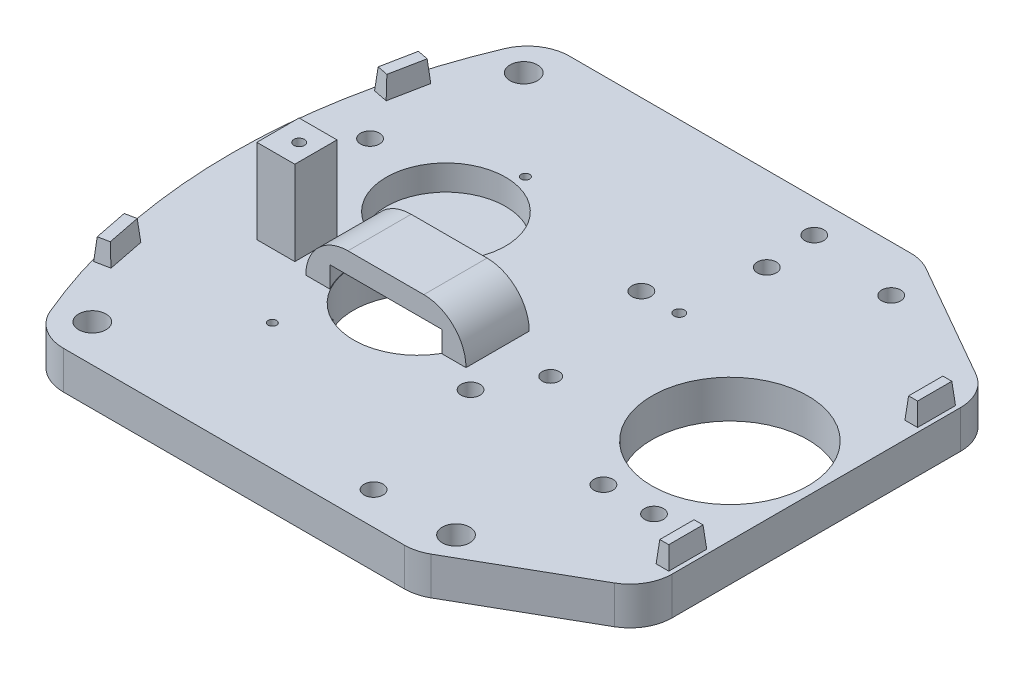
SolidWorks part; units mm, degrees
ref_plane "Front" through (0, 0, 0) normal (0, 0, 1) x (1, 0, 0)
ref_plane "Top" through (0, 0, 0) normal (0, 1, 0) x (1, 0, 0)
ref_plane "Right" through (0, 0, 0) normal (1, 0, 0) x (0, 0, -1)
sketch "Sketch1" plane through (0, 0, 0) normal (0, 1, 0) x (1, 0, 0)
  line L0 (125, 60) -> (3.8854, 60) construction
  line L1 (0, 0) -> (125, 0)
  line L2 (0, 0) -> (0, 120)
  line L3 (0, 120) -> (125, 120)
  line L4 (125, 0) -> (125, 120)
  line L5 (3.8854, 127.5) -> (3.8854, -7.5) construction
  arc A0 (3.8854, 127.5) -> (3.8854, -7.5) centre (125, 60) ccw
  dimension "D1" = 125
  dimension "D2" = 120
  dimension "D3" = 135
extrude "Top_Base" add sketch "Sketch1" along normal blind 9 contours L2 A0 | L1 L4 L3 L2 region at (62.5, 0, -60) region at (-5.4854, 0, -60)
sketch "Fingers_Position" plane through (0, 9, 0) normal (0, 1, 0) x (1, 0, 0)
  line L5 (67.75, 3.25) -> (12.75, 3.25) construction
  line L6 (67.75, 3.25) -> (67.75, 35.25) construction
  line L7 (67.75, 35.25) -> (12.75, 35.25) construction
  line L8 (12.75, 3.25) -> (12.75, 35.25) construction
  line L10 (67.75, 19.25) -> (26, 19.25) construction
  line L11 (77.75, 104.5) -> (77.75, 49.5) construction
  line L12 (35.75, 35.25) -> (35.75, 3.25) construction
  line L13 (40.75, 35.25) -> (40.75, 3.25) construction
  line L14 (125, 60) -> (-13.6542, 60) construction
  line L15 (35.75, 84.75) -> (35.75, 116.75) construction
  line L16 (26, 19.25) -> (26, 30) construction
  line L18 (77.75, 49.5) -> (109.75, 49.5) construction
  line L19 (109.75, 49.5) -> (109.75, 104.5) construction
  line L20 (109.75, 104.5) -> (77.75, 104.5) construction
  line L21 (92.5, 69) -> (92.5, 31) construction
  line L22 (92.5, 31) -> (116.5, 31) construction
  line L23 (116.5, 31) -> (116.5, 69) construction
  line L24 (116.5, 69) -> (92.5, 69) construction
  line L25 (93.75, 104.5) -> (93.75, 60) construction
  line L26 (104.5, 31) -> (104.5, 60) construction
  line L27 (26, 100.75) -> (26, 90) construction
  line L28 (40.75, 84.75) -> (40.75, 116.75) construction
  line L29 (67.75, 100.75) -> (26, 100.75) construction
  line L30 (12.75, 116.75) -> (12.75, 84.75) construction
  line L31 (67.75, 84.75) -> (12.75, 84.75) construction
  line L32 (67.75, 116.75) -> (67.75, 84.75) construction
  line L33 (67.75, 116.75) -> (12.75, 116.75) construction
  line L34 (26, 72.5) -> (26, 47.5) construction
  line L35 (92.5, 36) -> (98.5, 36) construction
  line L36 (98.5, 36) -> (98.5, 31) construction
  line L37 (116.5, 36) -> (110.5, 36) construction
  line L38 (110.5, 36) -> (110.5, 31) construction
  line L39 (93.75, 60) -> (104.5, 60) construction
  line L40 (77.75, 77.5) -> (109.75, 77.5) construction
  line L41 (125, 0) -> (125, 120) construction
  line L42 (67.75, 75.75) -> (58.75, 75.75) construction
  line L43 (67.75, 35.25) -> (58.75, 35.25) construction
  line L44 (67.75, 35.25) -> (67.75, 44.25) construction
  line L45 (67.75, 44.25) -> (58.75, 44.25) construction
  line L46 (58.75, 35.25) -> (58.75, 44.25) construction
  line L47 (58.75, 84.75) -> (58.75, 75.75) construction
  line L48 (67.75, 84.75) -> (58.75, 84.75) construction
  line L49 (67.75, 84.75) -> (67.75, 75.75) construction
  circle A1 centre (26, 30) radius 16.25 construction
  circle A3 centre (26, 30) radius 17.5 construction
  circle A5 centre (26, 30) radius 15 construction
  circle A6 centre (104.5, 60) radius 9 construction
  circle A7 centre (104.5, 60) radius 17.75 construction
  circle A8 centre (26, 30) radius 1 construction
  circle A9 centre (39.1696, 51.25) radius 7.5 construction
  circle A10 centre (39.1696, 51.25) radius 8.75 construction
  circle A11 centre (39.1696, 51.25) radius 10 construction
  circle A12 centre (39.1696, 68.75) radius 10 construction
  circle A13 centre (39.1696, 68.75) radius 8.75 construction
  circle A14 centre (39.1696, 68.75) radius 7.5 construction
  circle A15 centre (26, 90) radius 1 construction
  circle A16 centre (26, 90) radius 15 construction
  circle A17 centre (26, 90) radius 17.5 construction
  circle A18 centre (26, 90) radius 16.25 construction
  circle A19 centre (98.5, 36) radius 2.25 construction
  circle A20 centre (110.5, 36) radius 2.25 construction
  arc A21 (0, 120) -> (0, 0) centre (125, 60) ccw construction
  dimension "D3" = 32.5
  dimension "D4" = 35
  dimension "D6" = 30
  dimension "D10" = 18
  dimension "D11" = 35.5
  dimension "D19" = 2
  dimension "D20" = 20
  dimension "D21" = 17.5
  dimension "D22" = 15
  dimension "D29" = 4.5
  dimension "D5" = 32
  dimension "D7" = 55
  dimension "D8" = 24
  dimension "D9" = 38
  dimension "D14" = 10
  dimension "D2" = 27
  dimension "D15" = 55
  dimension "D16" = 32
  dimension "D17" = 41.75
  dimension "D18" = 10.75
  dimension "D23" = 25
  dimension "D13" = 29
  dimension "D25" = 6
  dimension "D26" = 6
  dimension "D27" = 5
  dimension "D28" = 5
  dimension "D12" = 44.5
  dimension "D30" = 10.75
  dimension "D31" = 27
  dimension "D24" = 8.5
  dimension "D32" = 32
  dimension "D33" = 9
  dimension "D34" = 9
sketch "Intermediate_Gear_Position" plane through (0, 9, 0) normal (0, 1, 0) x (1, 0, 0)
  line L0 (-5.25, 73.4139) -> (23.75, 73.4139) construction
  line L1 (35.75, 84.75) -> (35.75, 116.75) construction
  line L2 (32.75, 85.4139) -> (32.75, 61.4139) construction
  line L3 (-0.25, 79.4139) -> (-0.25, 85.4139) construction
  line L4 (32.75, 85.4139) -> (-5.25, 85.4139) construction
  line L6 (-5.25, 85.4139) -> (-5.25, 61.4139) construction
  line L7 (32.75, 61.4139) -> (-5.25, 61.4139) construction
  line L21 (-0.25, 67.4139) -> (-0.25, 61.4139) construction
  circle A0 centre (39.1696, 51.25) radius 14 construction
  circle A4 centre (39.1696, 51.25) radius 15 construction
  circle A6 centre (23.75, 73.4139) radius 14 construction
  circle A8 centre (39.1696, 51.25) radius 13 construction
  circle A10 centre (-0.25, 67.4139) radius 2.25 construction
  circle A11 centre (23.75, 73.4139) radius 13 construction
  circle A12 centre (-0.25, 79.4139) radius 2.25 construction
  circle A13 centre (23.75, 73.4139) radius 12 construction
  dimension "D2" = 30
  dimension "D6" = 28
  dimension "D4" = 26
  dimension "D18" = 4.5
  dimension "D22" = 4.5
  dimension "D3" = 28
  dimension "D10" = 26
  dimension "D11" = 24
  dimension "D8" = 38
  dimension "D5" = 6
  dimension "D7" = 24
  dimension "D16" = 5
  dimension "D19" = 6
  dimension "D21" = 5
  dimension "D9" = 29
  dimension "D12" = 3
sketch "Sketch5" plane through (0, 9, 0) normal (0, 1, 0) x (1, 0, 0)
  circle A1 centre (23.75, 73.4139) radius 14.15
  dimension "D1" = 28.3
extrude "Drive_Gear_Hole" cut sketch "Sketch5" against normal blind 6
sketch "Sketch8" plane through (0, 9, 0) normal (0, 1, 0) x (1, 0, 0)
  circle A1 centre (104.5, 60) radius 18.5
  dimension "D2" = 37
sketch "Sketch28" plane through (0, 9, 0) normal (0, 1, 0) x (1, 0, 0)
  circle A0 centre (39.1696, 51.25) radius 15.15
  dimension "D1" = 30.3
extrude "Two_Stage_Gear_Hole" cut sketch "Sketch28" against normal through all
extrude "XL320_Finger_Knuckle_Mount" cut sketch "Sketch8" against normal through all
sketch "XL320_Mount_Holes" plane through (0, 9, 0) normal (0, 1, 0) x (1, 0, 0)
  line L0 (116.5, 36) -> (110.5, 36) construction
  circle A13 centre (110.5, 36) radius 2.25
  circle A15 centre (98.5, 36) radius 2.25
  circle A16 centre (-0.25, 79.4139) radius 2.25
  circle A17 centre (-0.25, 67.4139) radius 2.25
  dimension "D5" = 4.5
sketch "AX12_Mount_Holes" plane through (0, 9, 0) normal (0, 1, 0) x (1, 0, 0)
  line L0 (67.75, 116.75) -> (72.25, 116.75) construction
  line L1 (67.75, 116.75) -> (12.75, 116.75) construction
  line L2 (72.25, 116.75) -> (72.25, 112.25) construction
  line L3 (67.75, 84.75) -> (67.75, 80.25) construction
  line L4 (67.75, 80.25) -> (63.25, 80.25) construction
  line L5 (93.75, 104.5) -> (93.75, 109) construction
  line L7 (109.75, 104.5) -> (77.75, 104.5) construction
  line L8 (77.75, 104.5) -> (73.25, 104.5) construction
  line L9 (73.25, 104.5) -> (73.25, 100) construction
  line L10 (67.75, 35.25) -> (67.75, 39.75) construction
  line L11 (67.75, 39.75) -> (63.25, 39.75) construction
  line L12 (67.75, 3.25) -> (72.25, 3.25) construction
  line L13 (67.75, 3.25) -> (12.75, 3.25) construction
  line L14 (72.25, 3.25) -> (72.25, 7.75) construction
  circle A4 centre (72.25, 112.25) radius 2.25
  circle A5 centre (63.25, 80.25) radius 2.25
  circle A6 centre (73.25, 100) radius 2.25
  circle A7 centre (93.75, 109) radius 2.25
  circle A8 centre (63.25, 39.75) radius 2.25
  circle A9 centre (72.25, 7.75) radius 2.25
  dimension "D2" = 4.5
  dimension "D1" = 4.5
sketch "Sketch26" plane through (0, 9, 0) normal (0, -1, 0) x (1, 0, 0)
  line L0 (26, -12.5) -> (26, -30) construction
  line L2 (-13.6542, -60) -> (125, -60) construction
  circle A0 centre (26, -30) radius 17.5 construction
  circle A1 centre (26, -30) radius 1
  circle A2 centre (26, -90) radius 1
  dimension "D2" = 2
extrude "String_Holes" cut sketch "Sketch26" along normal through all
extrude "XL320_Mount_Holes_(M4)" cut sketch "XL320_Mount_Holes" against normal through all
extrude "AX12_Mount_Holes_(M4)" cut sketch "AX12_Mount_Holes" against normal through all
sketch "Sketch27" plane through (0, 0, 0) normal (0, -1, 0) x (1, 0, 0)
  line L0 (110.5, -31.9585) -> (107, -33.9793)
  line L2 (107, -33.9793) -> (107, -38.0207)
  line L3 (107, -38.0207) -> (110.5, -40.0415)
  line L5 (110.5, -40.0415) -> (114, -38.0207)
  line L6 (114, -38.0207) -> (114, -33.9793)
  line L8 (114, -33.9793) -> (110.5, -31.9585)
  line L13 (110.5, -31.9585) -> (110.5, -40.0415) construction
  line L14 (107, -33.9793) -> (114, -38.0207) construction
  line L16 (114, -33.9793) -> (107, -38.0207) construction
  line L17 (98.5, -31.9585) -> (95, -33.9793)
  line L18 (95, -33.9793) -> (102, -38.0207) construction
  line L19 (95, -33.9793) -> (95, -38.0207)
  line L20 (102, -33.9793) -> (95, -38.0207) construction
  line L21 (98.5, -31.9585) -> (98.5, -40.0415) construction
  line L22 (102, -38.0207) -> (102, -33.9793)
  line L23 (95, -38.0207) -> (98.5, -40.0415)
  line L24 (98.5, -40.0415) -> (102, -38.0207)
  line L25 (102, -33.9793) -> (98.5, -31.9585)
  line L26 (3.25, -65.3931) -> (-0.25, -63.3724)
  line L27 (3.25, -69.4346) -> (3.25, -65.3931)
  line L28 (-3.75, -65.3931) -> (-3.75, -69.4346)
  line L29 (-0.25, -63.3724) -> (-0.25, -71.4553) construction
  line L30 (-3.75, -65.3931) -> (3.25, -69.4346) construction
  line L31 (-0.25, -63.3724) -> (-3.75, -65.3931)
  line L32 (-0.25, -71.4553) -> (3.25, -69.4346)
  line L33 (-3.75, -69.4346) -> (-0.25, -71.4553)
  line L34 (3.25, -65.3931) -> (-3.75, -69.4346) construction
  line L35 (-3.75, -77.3931) -> (3.25, -81.4346) construction
  line L36 (-3.75, -77.3931) -> (-3.75, -81.4346)
  line L37 (-0.25, -83.4553) -> (3.25, -81.4346)
  line L38 (-0.25, -75.3724) -> (-3.75, -77.3931)
  line L39 (3.25, -81.4346) -> (3.25, -77.3931)
  line L40 (-0.25, -75.3724) -> (-0.25, -83.4553) construction
  line L41 (3.25, -77.3931) -> (-0.25, -75.3724)
  line L42 (3.25, -77.3931) -> (-3.75, -81.4346) construction
  line L43 (-3.75, -81.4346) -> (-0.25, -83.4553)
  circle A4 centre (110.5, -36) radius 3.5 construction
  circle A5 centre (98.5, -36) radius 3.5 construction
  circle A6 centre (98.5, -36) radius 2.25 construction
  circle A7 centre (-0.25, -67.4139) radius 3.5 construction
  circle A8 centre (-0.25, -67.4139) radius 2.25 construction
  circle A9 centre (-0.25, -79.4139) radius 3.5 construction
  circle A21 centre (-0.25, -79.4139) radius 2.25 construction
  dimension "D1" = 7
  dimension "D3" = 7
  dimension "D5" = 7
  dimension "D7" = 7
  dimension "D2" = 60
  dimension "D4" = 60
  dimension "D6" = 60
  dimension "D8" = 60
extrude "Nuts_(M4)" cut sketch "Sketch27" against normal blind 5
sketch "Sketch34" plane through (0, 0, 0) normal (0, -1, 0) x (1, 0, 0)
  circle A0 centre (26, -30) radius 15
  circle A1 centre (26, -90) radius 15
  circle A2 centre (26, -90) radius 11.75 construction
  dimension "D1" = 30
  dimension "D2" = 23.5
extrude "Holes_For_M4_In_Finger_Gear" cut sketch "Sketch34" against normal blind 2
sketch "Sketch31" plane through (0, 9, 0) normal (0, 1, 0) x (1, 0, 0)
  line L1 (58.1696, 43.75) -> (20.1696, 43.75)
  line L2 (58.1696, 43.75) -> (58.1696, 58.75)
  line L3 (58.1696, 58.75) -> (20.1696, 58.75)
  line L4 (20.1696, 43.75) -> (20.1696, 58.75)
  line L5 (58.1696, 43.75) -> (20.1696, 58.75) construction
  line L6 (58.1696, 58.75) -> (20.1696, 43.75) construction
  point P0 (39.1696, 51.25)
  dimension "D1" = 38
  dimension "D2" = 15
extrude "Boss-Extrude1" add sketch "Sketch31" along normal blind 10
sketch "Sketch32" plane through (0, 9, 0) normal (0, -1, 0) x (1, 0, 0)
  circle A0 centre (39.1696, -51.25) radius 15.25
  dimension "D1" = 30.5
extrude "Cut-Extrude5" cut sketch "Sketch32" against normal blind 5
sketch "Sketch33" plane through (0, 14, 0) normal (0, -1, 0) x (1, 0, 0)
  circle A0 centre (39.1696, -51.25) radius 1
  dimension "D1" = 2
extrude "Cut-Extrude6" cut sketch "Sketch33" against normal blind 2.5
fillet "Fillet2" radius 10 2 edges at (58.1696, 19, -51.25) (20.1696, 19, -51.25)
sketch "Sketch36" plane through (0, 9, 0) normal (0, 1, 0) x (1, 0, 0)
  line L0 (90, 120) -> (125, 100)
  line L1 (0, 120) -> (125, 120) construction
  line L2 (125, 0) -> (125, 120) construction
  line L3 (125, 100) -> (125, 120)
  line L4 (125, 120) -> (90, 120)
  line L5 (-13.6542, 60) -> (125, 60) construction
  line L6 (125, 0) -> (90, 0)
  line L7 (125, 20) -> (125, 0)
  line L8 (90, 0) -> (125, 20)
  dimension "D1" = 35
  dimension "D4" = 20
extrude "Cut-Extrude8" cut sketch "Sketch36" against normal through all
fillet "Fillet4" radius 10 6 edges at (0, 4.5, 0) (90, 4.5, 0) (125, 4.5, -20) (125, 4.5, -100) (90, 4.5, -120) (0, 4.5, -120)
sketch "Sketch37" plane through (0, 9, 0) normal (0, 1, 0) x (1, 0, 0)
  line L0 (6.4592, 120) -> (6.4592, 0) construction
  line L1 (87.3444, 120) -> (87.3444, 0) construction
  line L2 (6.4592, 111.1529) -> (4.4592, 111.1529) construction
  line L3 (4.4592, 111.1529) -> (0.9304, 118.3326) construction
  line L4 (-13.6542, 60) -> (125, 60) construction
  line L5 (4.4592, 8.8471) -> (0.9304, 1.6674) construction
  line L6 (6.4592, 8.8471) -> (4.4592, 8.8471) construction
  line L7 (91.3444, 8.2056) -> (87.3444, 8.2056) construction
  line L10 (91.3444, 8.2056) -> (89.911, 0.335) construction
  arc A0 (87.3444, 0) -> (92.3057, 1.3176) centre (87.3444, 10) ccw construction
  circle A1 centre (4.4592, 111.1529) radius 3.25
  arc A2 (6.4592, 120) -> (-2.7547, 113.8864) centre (6.4592, 110) ccw construction
  circle A3 centre (4.4592, 8.8471) radius 3.25
  circle A4 centre (91.3444, 8.2056) radius 3.25
  dimension "D1" = 6.5
  dimension "D4" = 6.5
  dimension "D2" = 8
  dimension "D3" = 2
  dimension "D5" = 4
  dimension "D6" = 8
extrude "Connect_Holes_(M6)" cut sketch "Sketch37" against normal blind 10
sketch "Sketch41" plane through (0, 9, 0) normal (0, 1, 0) x (1, 0, 0)
  line L0 (125, 60) -> (-13.6542, 60) construction
  line L1 (125, 60) -> (65, 60) construction
  line L2 (125, 25.8032) -> (125, 94.1968) construction
  line L3 (65, 60) -> (65, 52) construction
  line L4 (65, 52) -> (70, 52) construction
  circle A0 centre (65, 60) radius 2 construction
  circle A1 centre (70, 52) radius 2
  point P10 (73.4205, 51.7742)
  dimension "D2" = 4
  dimension "D3" = 4
  dimension "D1" = 60
  dimension "D4" = 8
  dimension "D5" = 5
extrude "Connect_To_House_(M4)" cut sketch "Sketch41" against normal through all
sketch "Sketch42" plane through (0, 9, 0) normal (0, 1, 0) x (1, 0, 0)
  line L5 (-13.6542, 60) -> (125, 60) construction
  line L6 (124, 26) -> (121, 26)
  line L7 (124, 26) -> (124, 35)
  line L8 (124, 35) -> (121, 35)
  line L9 (121, 26) -> (121, 35)
  line L10 (-13.6542, 60) -> (-3.3496, 8.0542) construction
  line L11 (-9.5334, 30.2329) -> (-6.1003, 30.9139)
  line L12 (-6.1003, 30.9139) -> (-4.349, 22.0859)
  line L13 (-4.349, 22.0859) -> (-7.7822, 21.4049)
  line L14 (-7.7822, 21.4049) -> (-9.5334, 30.2329)
  line L15 (125, 25.8032) -> (125, 94.1968) construction
  line L16 (-4.349, 97.9141) -> (-7.7822, 98.5951)
  line L17 (-6.1003, 89.0861) -> (-4.349, 97.9141)
  line L18 (-7.7822, 98.5951) -> (-9.5334, 89.7671)
  line L19 (-9.5334, 89.7671) -> (-6.1003, 89.0861)
  line L20 (124, 94) -> (121, 94)
  line L21 (121, 94) -> (121, 85)
  line L22 (124, 85) -> (121, 85)
  line L23 (124, 94) -> (124, 85)
  arc A1 (-2.7547, 6.1136) -> (6.4592, 0) centre (6.4592, 10) ccw construction
  point P16 (-7.8168, 30.5734)
  dimension "D1" = 3
  dimension "D2" = 9
  dimension "D3" = 25
  dimension "D4" = 9
  dimension "D5" = 3.5
  dimension "D6" = 30
  dimension "D7" = 1
extrude "Housing_Fits" add sketch "Sketch42" along normal blind 5 draft 5
sketch "Sketch43" plane through (0, 0, 0) normal (0, -1, 0) x (1, 0, 0)
  circle A0 centre (39.1696, -68.75) radius 1
  dimension "D1" = 2
extrude "M2_Shaft_Hole" cut sketch "Sketch43" against normal blind 2
sketch "Sketch54" plane through (0, 2, 0) normal (0, -1, 0) x (1, 0, 0)
  circle A0 centre (26, -30) radius 1.5
  circle A1 centre (26, -90) radius 1.5
  dimension "D1" = 3
extrude "Hollow_Shaft_Hole" cut sketch "Sketch54" against normal blind 5
sketch "Sketch46" plane through (0, 9, 0) normal (0, 1, 0) x (1, 0, 0)
  line L0 (67.75, 84.75) -> (76.75, 75.75) construction
  line L1 (67.75, 84.75) -> (76.75, 84.75) construction
  line L2 (67.75, 84.75) -> (67.75, 75.75) construction
  line L3 (67.75, 75.75) -> (76.75, 75.75) construction
  line L4 (76.75, 84.75) -> (76.75, 75.75) construction
  line L5 (76.75, 84.75) -> (67.75, 75.75) construction
  circle A0 centre (72.25, 80.25) radius 1.25
  dimension "D3" = 2.5
  dimension "D1" = 9
  dimension "D2" = 9
extrude "Cut-Extrude11" cut sketch "Sketch46" against normal through all
sketch "Sketch47" plane through (0, 0, 0) normal (0, -1, 0) x (1, 0, 0)
  circle A0 centre (72.25, -80.25) radius 2.25
  dimension "D1" = 4.5
extrude "Cut-Extrude12" cut sketch "Sketch47" against normal blind 5
sketch "Sketch48" plane through (0, 0, 0) normal (0, -1, 0) x (1, 0, 0)
  circle A0 centre (72.25, -80.25) radius 2.875
  dimension "D1" = 5.75
extrude "Cut-Extrude13" cut sketch "Sketch48" against normal blind 0.75
sketch "Sketch49" plane through (0, 9, 0) normal (0, 1, 0) x (1, 0, 0)
  line L0 (-13.6542, 60) -> (12.1321, 60) construction
  line L1 (125, 60) -> (-13.6542, 60) construction
  line L2 (12.1321, 60) -> (12.1321, 50.2322) construction
  line L3 (12.1321, 50.2322) -> (12.1321, 45.2322) construction
  line L4 (12.1321, 45.2322) -> (7.0937, 45.2322)
  line L5 (7.0937, 45.2322) -> (7.0937, 55.2322)
  line L6 (7.0937, 55.2322) -> (12.1321, 55.2322)
  line L7 (12.1321, 55.2322) -> (16.0937, 55.2322)
  line L8 (16.0937, 55.2322) -> (16.0937, 45.2322)
  line L9 (16.0937, 45.2322) -> (12.1321, 45.2322)
  arc A0 (-2.7547, 113.8864) -> (-2.7547, 6.1136) centre (125, 60) ccw construction
  circle A1 centre (12.1321, 50.2322) radius 1.25
  dimension "D3" = 2.5
  dimension "D1" = 25.7863
  dimension "D2" = 9.7678
  dimension "D4" = 5
  dimension "D5" = 5.0384
  dimension "D6" = 10
  dimension "D7" = 3.9616
extrude "Boss-Extrude2" add sketch "Sketch49" along normal blind 20 contours L9 L8 L7 L6 L5 L4 A1 region at (9.6129, 9, -45.3667)
sketch "Sketch51" plane through (0, 9, 0) normal (0, 1, 0) x (1, 0, 0)
  circle A0 centre (12.1321, 50.2322) radius 1.25
  dimension "D1" = 2.5
extrude "Cut-Extrude14" cut sketch "Sketch51" against normal through all
sketch "Sketch52" plane through (0, 0, 0) normal (0, -1, 0) x (1, 0, 0)
  circle A0 centre (12.1321, -50.2322) radius 2.25
  dimension "D1" = 4.5
extrude "Cut-Extrude15" cut sketch "Sketch52" against normal blind 5
sketch "Sketch53" plane through (0, 0, 0) normal (0, -1, 0) x (1, 0, 0)
  circle A0 centre (12.1321, -50.2322) radius 2.875
  dimension "D1" = 5.75
extrude "Cut-Extrude16" cut sketch "Sketch53" against normal blind 0.75
equation "\"od1\"= 35'outside diameter finger"
equation "\"n1\"= 26'number of teeth finger"
equation "\"m1\"= \"od1\" / ( \"n1\" + 2 )'module finger"
equation "\"p1\"= \"m1\" * pi'pitch finger"
equation "\"d1\"= \"m1\" * \"n1\"'primitive diameter finger"
equation "\"da1\"= \"d1\" + 2 * \"m1\"'head diamater finger"
equation "\"df1\"= \"d1\" - 2 * \"m1\"'foot diameter finger"
equation "\"od2\"= 20'outside diameter intermediate"
equation "\"n2\"= 14'number of teeth intermediate"
equation "\"m2\"= \"od2\" / ( \"n2\" + 2 )'module intermediate"
equation "\"p2\"= \"m2\" * pi'pitch intermediate"
equation "\"d2\"= \"m2\" * \"n2\"'primitive diameter intermediate"
equation "\"da2\"= \"d2\" + 2 * \"m2\"'head diamater intermediate"
equation "\"df2\"= \"d2\" - 2 * \"m2\"'foot diameter intermediate"
equation "\"od3\"= 30'outside diameter top"
equation "\"n3\"= 28'number of teeth top"
equation "\"m3\"= \"od3\" / ( \"n3\" + 2 )'module top"
equation "\"p3\"= \"m3\" * pi'pitch top"
equation "\"d3\"= \"m3\" * \"n3\"'primitive diameter top"
equation "\"da3\"= \"d3\" + 2 * \"m3\"'head diamater top"
equation "\"df3\"= \"d3\" - 2 * \"m3\"'foot diameter top"
equation "\"od4\"= 28'outside diameter drive"
equation "\"n4\"= 26'number of teeth drive"
equation "\"m4\"= \"od4\" / ( \"n4\" + 2 )'module drive"
equation "\"p4\"= \"m4\" * pi'pitch drive"
equation "\"d4\"= \"m4\" * \"n4\"'primitive diameter drive"
equation "\"da4\"= \"d4\" + 2 * \"m4\"'head diamater drive"
equation "\"df4\"= \"d4\" - 2 * \"m4\"'foot diameter drive"
equation "\"D4@Fingers_Position\"=\"da1\""
equation "\"D3@Fingers_Position\"=\"d1\""
equation "\"D6@Fingers_Position\"=\"df1\""
equation "\"D20@Fingers_Position\"=\"da2\""
equation "\"D21@Fingers_Position\"=\"d2\""
equation "\"D22@Fingers_Position\"=\"df2\""
equation "\"D3@Intermediate_Gear_Position\"=\"d3\""
equation "\"D2@Intermediate_Gear_Position\"=\"da3\""
equation "\"D4@Intermediate_Gear_Position\"=\"df3\""
equation "\"D6@Intermediate_Gear_Position\"=\"da4\""
equation "\"D10@Intermediate_Gear_Position\"=\"d4\""
equation "\"D11@Intermediate_Gear_Position\"=\"df4\""
equation "\"D1@Sketch34\"=\"df1\""
